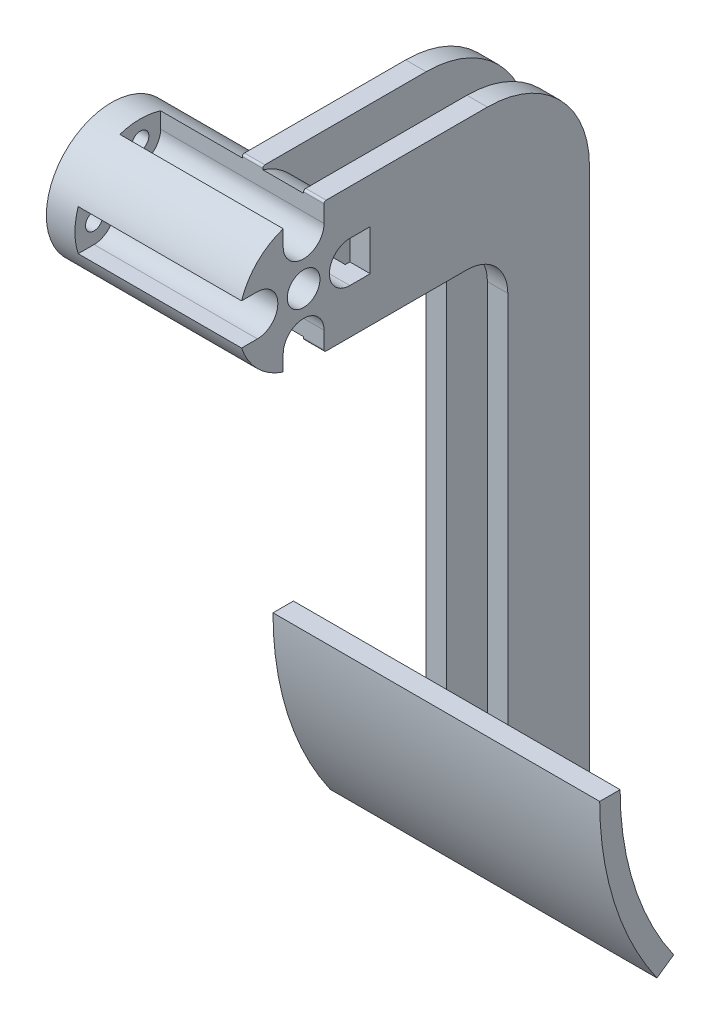
SolidWorks part; units mm, degrees
ref_plane "Front Plane" through (0, 0, 0) normal (0, 0, 1) x (1, 0, 0)
ref_plane "Top Plane" through (0, 0, 0) normal (0, 1, 0) x (1, 0, 0)
ref_plane "Right Plane" through (0, 0, 0) normal (1, 0, 0) x (0, 0, -1)
sketch "Sketch1" plane through (0, 0, 0) normal (1, 0, 0) x (0, 0, -1)
  line L0 (0, 16) -> (70, 16)
  line L1 (70, 16) -> (70, -160)
  line L2 (70, -160) -> (50, -160)
  line L3 (50, -160) -> (50, -16)
  line L4 (50, -16) -> (0, -16)
  arc A0 (0, 16) -> (0, -16) centre (0, 0) ccw
  dimension "D1" = 32
  dimension "D2" = 176
  dimension "D3" = 20
  dimension "D4" = 70
extrude "Boss-Extrude1" add sketch "Sketch1" along normal blind 20
sketch "Sketch2" plane through (0, 0, 0) normal (-1, 0, 0) x (0, 0, 1)
  circle A0 centre (0, 0) radius 16
extrude "Boss-Extrude2" add sketch "Sketch2" along normal blind 27
sketch "Sketch3" plane through (0, 16, 0) normal (0, 1, 0) x (1, 0, 0)
  line L0 (5, 70) -> (15, 70)
  line L1 (20, 70) -> (0, 70) construction
  line L2 (15, 70) -> (15, 16)
  line L3 (15, 16) -> (5, 16)
  line L4 (5, 16) -> (5, 70)
  line L5 (20, 70) -> (20, 0) construction
  line L6 (0, 70) -> (0, 0) construction
  dimension "D1" = 5
  dimension "D2" = 5
  dimension "D3" = 54
extrude "Cut-Extrude1" cut sketch "Sketch3" against normal through all
fillet "Fillet1" radius 16 2 edges at (10, -16, -16) (10, 16, -16)
sketch "Sketch5" plane through (-27, 0, 0) normal (-1, 0, 0) x (0, 0, 1)
  circle A0 centre (0, 0) radius 4
  dimension "D1" = 8
extrude "Cut-Extrude2" cut sketch "Sketch5" against normal through all
sketch "Sketch6" plane through (20, 0, 0) normal (1, 0, 0) x (0, 0, -1)
  line L0 (-24.5233, 0) -> (67.7131, 0) construction
  line L1 (0, 36.1144) -> (0, -37.0831) construction
  line L3 (0, 11.3137) -> (-11.3137, 0) construction
  line L4 (-11.3137, 0) -> (0, -11.3137) construction
  line L5 (0, -11.3137) -> (11.3137, 0) construction
  line L6 (11.3137, 0) -> (0, 11.3137) construction
  circle A0 centre (0, 0) radius 8 construction
  circle A1 centre (0, 11.3137) radius 2.1
  circle A2 centre (11.3137, 0) radius 2.1
  circle A3 centre (0, -11.3137) radius 2.1
  circle A4 centre (-11.3137, 0) radius 2.1
  dimension "D1" = 16
  dimension "D2" = 4.2
  dimension "D3" = 4.2
  dimension "D4" = 4.2
  dimension "D5" = 4.2
extrude "Cut-Extrude3" cut sketch "Sketch6" against normal through all
sketch "Sketch7" plane through (20, 0, 0) normal (1, 0, 0) x (0, 0, -1)
  line L0 (-5, 16.3137) -> (5, 16.3137)
  line L1 (-5, 11.3137) -> (-5, 16.3137)
  line L2 (5, 11.3137) -> (5, 16.3137)
  line L3 (11.3137, -5) -> (16.3137, -5)
  line L4 (16.3137, 5) -> (16.3137, -5)
  line L5 (11.3137, 5) -> (16.3137, 5)
  line L6 (-5, -11.3137) -> (-5, -16.3137)
  line L7 (5, -16.3137) -> (-5, -16.3137)
  line L8 (5, -11.3137) -> (5, -16.3137)
  line L9 (-11.3137, 5) -> (-16.3137, 5)
  line L10 (-16.3137, -5) -> (-16.3137, 5)
  line L11 (-11.3137, -5) -> (-16.3137, -5)
  arc A0 (-5, 11.3137) -> (5, 11.3137) centre (0, 11.3137) ccw
  arc A4 (11.3137, 5) -> (11.3137, -5) centre (11.3137, 0) ccw
  arc A5 (5, -11.3137) -> (-5, -11.3137) centre (0, -11.3137) ccw
  arc A6 (-11.3137, -5) -> (-11.3137, 5) centre (-11.3137, 0) ccw
  point P27 (0, 0)
  dimension "D1" = 10
  dimension "D2" = 4
  dimension "D5" = 5
extrude "Cut-Extrude5" cut sketch "Sketch7" against normal blind 40
fillet "Fillet3" radius 0.5 4 edges at (17.5, -16, -5) (2.5, -16, -5) (17.5, 16, -5) (2.5, 16, -5)
fillet "Fillet4" radius 10 2 edges at (17.5, -16, -50) (2.5, -16, -50)
fillet "Fillet5" radius 25 2 edges at (2.5, 16, -70) (17.5, 16, -70)
sketch "Sketch8" plane through (0, 0, -70) normal (0, 0, -1) x (-1, 0, 0)
  line L0 (-15, -35.1987) -> (-5, -35.1987)
  line L1 (-15, -160) -> (-15, -9) construction
  line L2 (-5, -160) -> (-5, -9) construction
  line L3 (-5, -35.1987) -> (-5, -40.1987)
  line L4 (-5, -40.1987) -> (-15, -40.1987)
  line L5 (-15, -40.1987) -> (-15, -35.1987)
  line L6 (-5, -15.1987) -> (-15, -15.1987) construction
  dimension "D1" = 20
  dimension "D2" = 5
extrude "Boss-Extrude3" add sketch "Sketch8" against normal blind 10
fillet "Fillet6" radius 2 4 edges at (5, -40.1987, -65) (15, -40.1987, -65) (15, -35.1987, -65) (5, -35.1987, -65)
sketch "Sketch9" plane through (20, 0, 0) normal (1, 0, 0) x (0, 0, -1)
  line L0 (50, -160) -> (50, -133.8746)
  line L4 (50, -160) -> (63.1559, -160)
  arc A0 (50, -133.8746) -> (63.1559, -160) centre (120, -115) ccw
  dimension "D3" = 145
  dimension "D1" = 70
  dimension "D2" = 45
  dimension "D4" = 26.1254
extrude "Cut-Extrude6" cut sketch "Sketch9" against normal through all
sketch "Sketch10" plane through (20, 0, 0) normal (1, 0, 0) x (0, 0, -1)
  line L2 (47.5, -115) -> (42.5, -115)
  line L3 (60.6115, -156.5843) -> (56.5157, -159.4522)
  line L4 (42.5, -115) -> (120, -115) construction
  line L5 (120, -115) -> (56.5157, -159.4522) construction
  arc A1 (47.5, -115) -> (60.6115, -156.5843) centre (120, -115) ccw
  arc A2 (42.5, -115) -> (56.5157, -159.4522) centre (120, -115) ccw
  dimension "D1" = 145
  dimension "D2" = 5
  dimension "D3" = 35
  dimension "D4" = 35
extrude "Boss-Extrude4" add sketch "Sketch10" along normal blind 30 and the other way blind 50
sketch "Sketch11" plane through (20, 0, 0) normal (1, 0, 0) x (0, 0, -1)
  line L0 (56.5157, -159.4522) -> (72.3948, -148.3335)
  line L1 (72.3948, -148.3335) -> (72.3948, -171.5703)
  line L2 (72.3948, -171.5703) -> (56.5157, -159.4522)
extrude "Cut-Extrude7" cut sketch "Sketch11" against normal blind 30
fillet "Fillet8" radius 2 4 edges at (0, -145.6915, -54.3168) (5, -145.6915, -54.3168) (15, -145.6915, -54.3168) (20, -145.6915, -54.3168)
